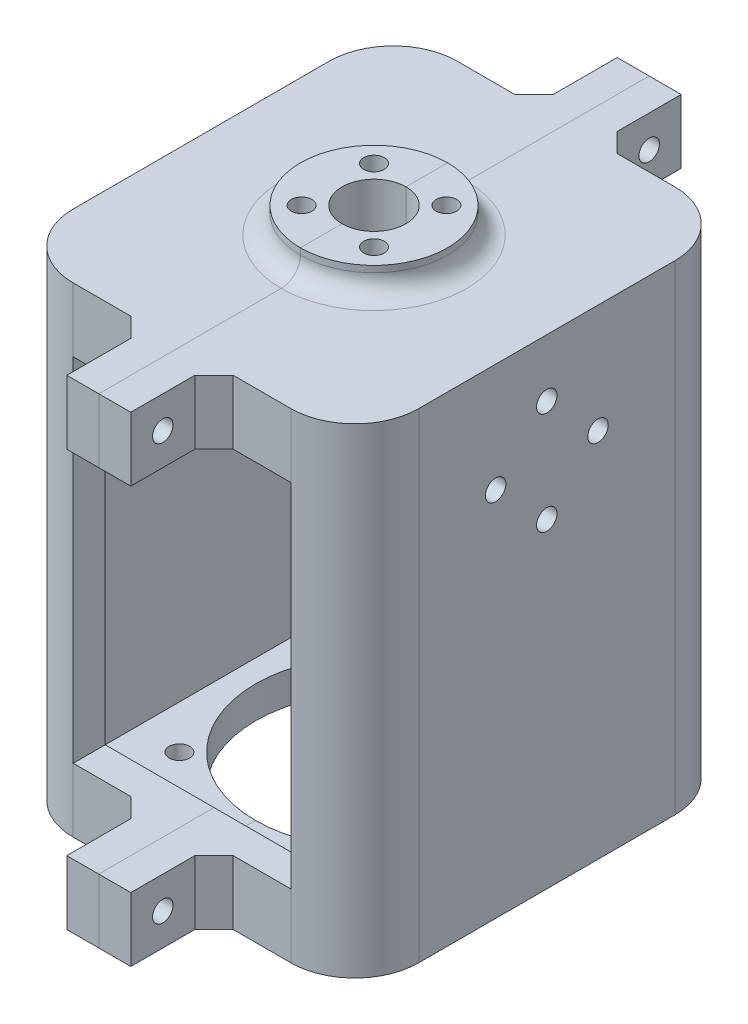
SolidWorks part; units mm, degrees
note: '?' marks a value the reader was unsure of.
ref_plane "Front Plane" through (0, 0, 0) normal (0, 0, 1) x (1, 0, 0)
ref_plane "Top Plane" through (0, 0, 0) normal (0, 1, 0) x (1, 0, 0)
ref_plane "Right Plane" through (0, 0, 0) normal (1, 0, 0) x (0, 0, -1)
sketch "Sketch2" plane through (0, 0, 0) normal (0, 1, 0) x (1, 0, 0)
  line L1 (-27, 30) -> (27, 30)
  line L2 (-27, 30) -> (-27, -30)
  line L3 (-27, -30) -> (27, -30)
  line L4 (27, 30) -> (27, -30)
  line L5 (-27, 30) -> (27, -30) construction
  line L6 (-27, -30) -> (27, 30) construction
  point P0 (0, 0)
  dimension "D1" = 54
  dimension "D2" = 60
extrude "Boss-Extrude1" add sketch "Sketch2" along normal blind 75
shell "Shell2" thickness 5
sketch "Sketch4" plane through (0, 0, 0) normal (0, -1, 0) x (1, 0, 0)
  circle A0 centre (0, 0) radius 18.5
  dimension "D1" = 37
extrude "Cut-Extrude2" cut sketch "Sketch4" against normal through all
sketch "Sketch5" plane through (0, 0, 0) normal (0, -1, 0) x (1, 0, 0)
  line L0 (0, 0) -> (0, 21.5) construction
  line L1 (15.2028, 15.2028) -> (0, 0) construction
  circle A0 centre (0, 0) radius 21.5 construction
  circle A1 centre (15.2028, 15.2028) radius 1.6
  dimension "D1" = 43
  dimension "D2" = 45
  dimension "D3" = 3.2
extrude "Cut-Extrude3" cut sketch "Sketch5" against normal through all
pattern_circular "CirPattern2" count 4 over 360 about axis through (0, 0, 0) along (0, 1, 0) of "Cut-Extrude3"
sketch "Sketch6" plane through (27, 0, 0) normal (1, 0, 0) x (0, 0, -1)
  line L0 (-30, 75) -> (30, 75) construction
  circle A0 centre (0, 58) radius 8 construction
  circle A1 centre (0, 66) radius 1.6
  dimension "D1" = 17
  dimension "D2" = 16
  dimension "D3" = 3.2
extrude "Cut-Extrude4" cut sketch "Sketch6" against normal through all
ref_axis "Axis1" through (27, 58, 0) along (1, 0, 0)?
pattern_circular "CirPattern3" count 4 over 360 about axis through (0, 58, 0) along (1, 0, 0) of "Cut-Extrude4"
sketch "Sketch7" plane through (0, 75, 0) normal (0, 1, 0) x (1, 0, 0)
  line L0 (-22, -25) -> (22, -25) construction
  line L1 (22, -25) -> (22, 25) construction
  line L2 (-22, 25) -> (-22, -25) construction
  line L3 (22, 25) -> (-22, 25) construction
  line L4 (-22, -25) -> (22, -25)
  line L5 (22, -25) -> (22, 25)
  line L6 (-22, 25) -> (-22, -25)
  line L7 (22, 25) -> (-22, 25)
extrude "Boss-Extrude2" add sketch "Sketch7" against normal blind 5
sketch "Sketch8" plane through (0, 75, 0) normal (0, 1, 0) x (1, 0, 0)
  circle A0 centre (0, 0) radius 5
  dimension "D1" = 10
extrude "Cut-Extrude5" cut sketch "Sketch8" against normal through all
sketch "Sketch9" plane through (0, 75, 0) normal (0, 1, 0) x (1, 0, 0)
  line L0 (0, 0) -> (0, 8) construction
  line L1 (0, 0) -> (5.6569, 5.6569) construction
  circle A0 centre (0, 0) radius 8 construction
  circle A1 centre (5.6569, 5.6569) radius 1.6
  dimension "D1" = 16
  dimension "D2" = 3.2
  dimension "D3" = 45
extrude "Cut-Extrude6" cut sketch "Sketch9" against normal through all
pattern_circular "CirPattern4" count 4 over 360 about axis through (0, 0, 0) along (0, 1, 0) of "Cut-Extrude6"
sketch "Sketch10" plane through (0, 0, -30) normal (0, 0, -1) x (-1, 0, 0)
  line L0 (-27, 75) -> (27, 0) construction
  line L1 (-27, 75) -> (27, 75) construction
  line L2 (-17, 65) -> (17, 65)
  line L3 (-17, 65) -> (-17, 10)
  line L4 (-17, 10) -> (17, 10)
  line L5 (17, 65) -> (17, 10)
  line L6 (-17, 65) -> (17, 10) construction
  line L7 (-17, 10) -> (17, 65) construction
  line L8 (27, 75) -> (27, 0) construction
  point P4 (0, 37.5)
  dimension "D1" = 10
  dimension "D2" = 10
extrude "Cut-Extrude7" cut sketch "Sketch10" against normal through all
fillet "Fillet1" radius 10 4 edges at (-27, 37.5, 30) (27, 37.5, 30) (-27, 37.5, -30) (27, 37.5, -30)
sketch "Sketch11" plane through (0, 0, 0) normal (1, 0, 0) x (0, 0, -1)
  line L0 (30, 75) -> (5, 75)
  line L1 (-5, 75) -> (-30, 75)
  line L2 (-5, 75) -> (-30, 75)
  line L3 (30, 75) -> (5, 75)
  line L4 (30, 75) -> (30, 65)
  line L5 (30, 75) -> (30, 65)
  line L6 (30, 75) -> (43, 75)
  line L7 (43, 75) -> (43, 65)
  line L8 (43, 65) -> (30, 65)
  line L9 (33, 75) -> (33, 65) construction
  line L10 (33, 65) -> (43, 75) construction
  circle A0 centre (38, 70) radius 1.6
  dimension "D3" = 3.2
  dimension "D1" = 13
  dimension "D2" = 3
extrude "Boss-Extrude3" add sketch "Sketch11" along normal mid plane 10 contours L8 L7 L6 L5 A0
ref_plane "Plane1" through (0, 37.5, 0) normal (0, 1, 0) x (1, 0, 0)
mirror "Mirror4" about plane through (0, 0, 0) normal (0, 0, 1) of "Boss-Extrude3" second plane through (0, 37.5, 0) second plane normal (0, 1, 0)
chamfer "Chamfer1" distance 3 angle 45 8 edges at (-5, 70, -30) (5, 70, -30) (5, 5, -30) (-5, 5, -30) (5, 70, 30) (-5, 70, 30) (-5, 5, 30) (5, 5, 30)
sketch "Sketch12" plane through (0, 75, 0) normal (0, 1, 0) x (1, 0, 0)
  circle A0 centre (0, 0) radius 11.5
  circle A1 centre (5.6569, -5.6569) radius 1.6 construction
  circle A2 centre (-5.6569, -5.6569) radius 1.6 construction
  circle A3 centre (-5.6569, 5.6569) radius 1.6 construction
  circle A4 centre (5.6569, 5.6569) radius 1.6 construction
  circle A5 centre (0, 0) radius 5 construction
  circle A6 centre (5.6569, -5.6569) radius 1.6
  circle A7 centre (-5.6569, -5.6569) radius 1.6
  circle A8 centre (-5.6569, 5.6569) radius 1.6
  circle A9 centre (5.6569, 5.6569) radius 1.6
  circle A10 centre (0, 0) radius 5
  dimension "D1" = 23
extrude "Boss-Extrude4" add sketch "Sketch12" along normal blind 4
fillet "Fillet2" radius 3 1 edges at (0, 75, 11.5)
split "Split1" trim tools "Right Plane" bodies to split 118 resulting bodies 116 117
